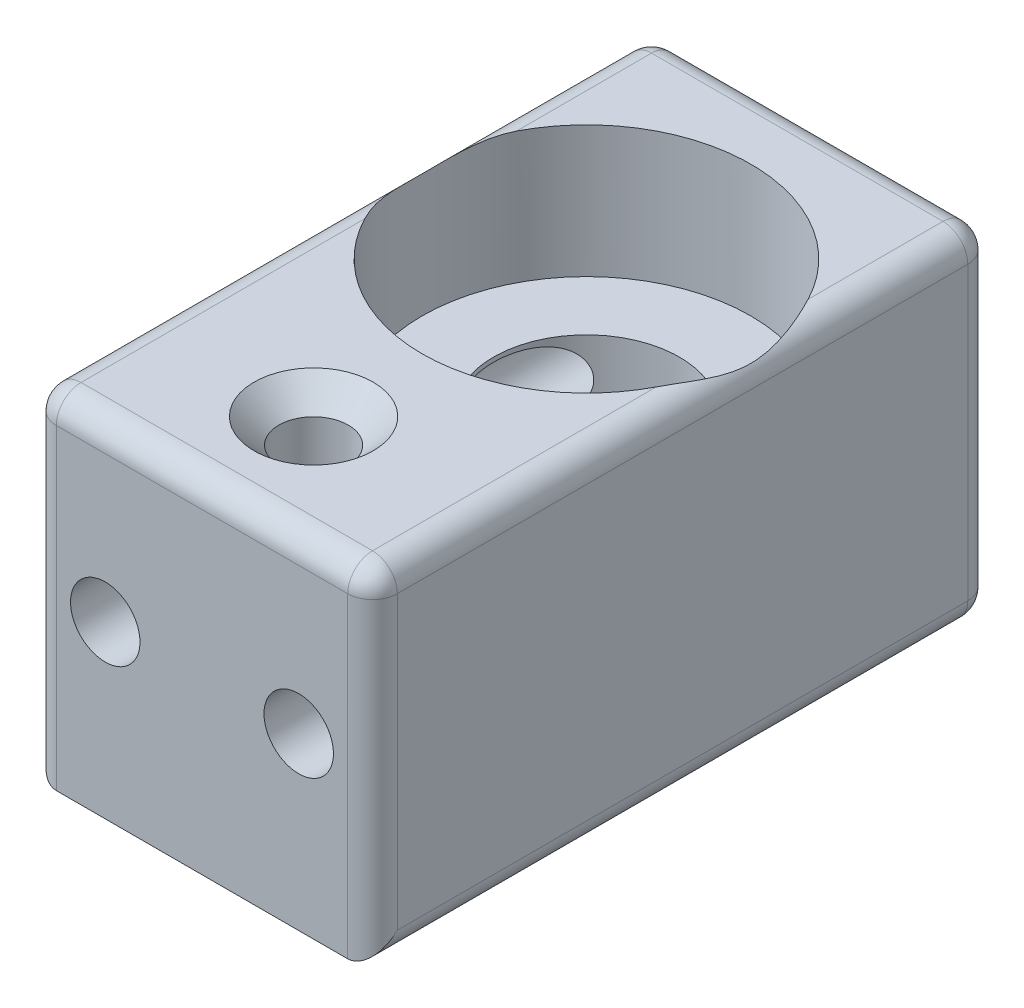
SolidWorks part; units mm, degrees
ref_plane "Front Plane" through (0, 0, 0) normal (0, 0, 1) x (1, 0, 0)
ref_plane "Top Plane" through (0, 0, 0) normal (0, 1, 0) x (1, 0, 0)
ref_plane "Right Plane" through (0, 0, 0) normal (1, 0, 0) x (0, 0, -1)
sketch "Sketch1" plane through (0, 0, 0) normal (0, 0, 1) x (1, 0, 0)
  line L1 (-6.875, -6.875) -> (6.875, -6.875)
  line L2 (-6.875, -6.875) -> (-6.875, 6.875)
  line L3 (-6.875, 6.875) -> (6.875, 6.875)
  line L4 (6.875, -6.875) -> (6.875, 6.875)
  line L5 (-6.875, -6.875) -> (6.875, 6.875) construction
  line L6 (-6.875, 6.875) -> (6.875, -6.875) construction
  point P0 (0, 0)
  dimension "D1" = 13.75
extrude "Boss-Extrude1" add sketch "Sketch1" along normal blind 25
ref_axis "Axis1" through (0, 0, -0.8) along (0, 0, 1)
sketch "Sketch3" plane through (0, 6.875, 0) normal (0, 1, 0) x (1, 0, 0)
  line L0 (0, -9.5) -> (0, 0) construction
  line L1 (6.875, 0) -> (-6.875, 0) construction
  circle A0 centre (0, -9.5) radius 6.5 construction
  circle A1 centre (0, -9.5) radius 3.75
  dimension "D1" = 13
  dimension "D3" = 7.5
  dimension "D2" = 3
extrude "Cut-Extrude2" cut sketch "Sketch3" against normal through all
sketch "Sketch4" plane through (0, 6.875, 0) normal (0, 1, 0) x (1, 0, 0)
  circle A0 centre (0, -9.5) radius 6.625
  dimension "D1" = 13.25
extrude "Cut-Extrude3" cut sketch "Sketch4" against normal blind 5.3
mirror "Mirror4" about plane through (0, 0, 0) normal (0, 1, 0) of "Cut-Extrude3"
sketch "Sketch8" plane through (0, 6.875, 0) normal (0, 1, 0) x (1, 0, 0)
  line L1 (0, 0) -> (0, -20.5) construction
  line L2 (6.875, 0) -> (-6.875, 0) construction
  circle A0 centre (0, -20.5) radius 1.4
  circle A1 centre (0, -9.5) radius 3.75 construction
  dimension "D1" = 11
  dimension "D2" = 2.8
extrude "Cut-Extrude6" cut sketch "Sketch8" against normal through all
sketch "Sketch9" plane through (0, 0, 0) normal (0, 0, -1) x (-1, 0, 0)
  line L0 (-3.9, 0) -> (0, 0) construction
  line L1 (-2, 1.1669) -> (-2, -1.0479) construction
  line L2 (0, 0.6668) -> (0, -0.643) construction
  circle A0 centre (-3.9, 0) radius 1.4
  dimension "D1" = 2.8
  dimension "D3" = 0.5
  dimension "D2" = 4
extrude "Cut-Extrude7" cut sketch "Sketch9" against normal through all
mirror "Mirror5" about plane through (0, 0, 0) normal (1, 0, 0) of "Cut-Extrude7"
chamfer "Chamfer1" distance 1 angle 45 2 edges at (0, -6.875, 21.9) (0, 6.875, 21.9)
fillet "Fillet3" [suppressed] radius 0.3
fillet "Fillet2" radius 1 11 edges at (0, 6.875, 0) (-6.875, 0, 0) (0, -6.875, 0) (6.875, 0, 0) (6.875, 0, 25) (-6.875, 0, 25) (0, 6.875, 25) (6.875, -6.875, 12.5) (-6.875, -6.875, 12.5) (6.875, 6.875, 12.5) (-6.875, 6.875, 12.5)
